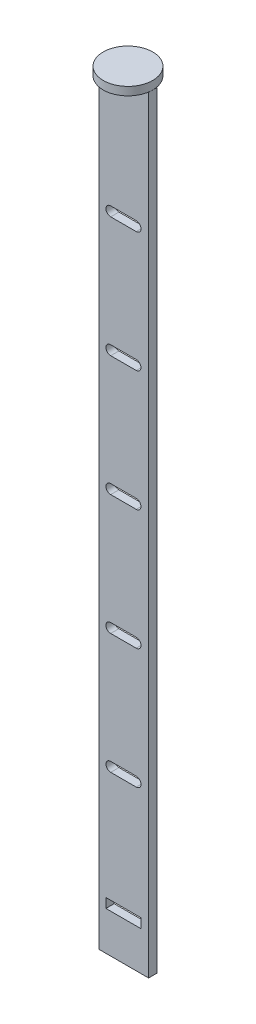
SolidWorks part; units mm, degrees
ref_plane "Front Plane" through (0, 0, 0) normal (0, 0, 1) x (1, 0, 0)
ref_plane "Top Plane" through (0, 0, 0) normal (0, 1, 0) x (1, 0, 0)
ref_plane "Right Plane" through (0, 0, 0) normal (1, 0, 0) x (0, 0, -1)
other "Configuration Table"
sketch "Sketch1" plane through (0, 0, 0) normal (1, 0, 0) x (0, 0, -1)
  line L1 (-495, 46.8667) -> (-501, 46.8667)
  line L2 (-495, 46.8667) -> (-495, 51.4667)
  line L3 (-495, 51.4667) -> (-501, 51.4667)
  line L4 (-501, 46.8667) -> (-501, 51.4667)
  line L5 (-495, 46.8667) -> (-501, 51.4667) construction
  line L6 (-495, 51.4667) -> (-501, 46.8667) construction
  point P0 (-498, 49.1667)
extrude "slot_0" add sketch "Sketch1" along normal blind 16.9953 from offset 20.3047 separate body
sketch "Sketch2" plane through (0, 0, 0) normal (1, 0, 0) x (0, 0, -1)
  line L1 (-496, 28) -> (-500, 28)
  line L2 (-496, 28) -> (-496, 400)
  line L3 (-496, 400) -> (-500, 400)
  line L4 (-500, 28) -> (-500, 400)
  line L5 (-496, 28) -> (-500, 400) construction
  line L6 (-496, 400) -> (-500, 28) construction
  point P0 (-498, 214)
extrude "bar" add sketch "Sketch2" along normal blind 24 from offset 17 separate body
combine bodies "Combine1" operation type subtract main body 103 bodies to subtract 102
sketch "Sketch3" plane through (0, 0, 0) normal (0, 0, 1) x (1, 0, 0)
  circle A0 centre (22.6047, 107.5) radius 2.3
extrude "slot_end_1" add sketch "Sketch3" along normal blind 6 from offset 495 separate body
combine bodies "Combine2" operation type subtract main body 104 bodies to subtract 105
sketch "Sketch4" plane through (0, 0, 0) normal (0, 0, 1) x (1, 0, 0)
  circle A0 centre (35, 107.5) radius 2.3
extrude "slot_end_b_1" add sketch "Sketch4" along normal blind 6 from offset 495 separate body
combine bodies "Combine3" operation type subtract main body 106 bodies to subtract 107
sketch "Sketch5" plane through (0, 0, 0) normal (0, 0, 1) x (1, 0, 0)
  line L1 (22.6047, 105.2) -> (35, 105.2)
  line L2 (22.6047, 105.2) -> (22.6047, 109.8)
  line L3 (22.6047, 109.8) -> (35, 109.8)
  line L4 (35, 105.2) -> (35, 109.8)
  line L5 (22.6047, 105.2) -> (35, 109.8) construction
  line L6 (22.6047, 109.8) -> (35, 105.2) construction
  circle A0 centre (35, 107.5) radius 2.3 construction
  point P0 (28.8024, 107.5)
extrude "Cut-Extrude1" cut sketch "Sketch5" against normal through all and the other way through all
sketch "Sketch6" plane through (0, 0, 0) normal (0, 0, 1) x (1, 0, 0)
  circle A0 centre (22.6047, 165.8333) radius 2.3
extrude "slot_end_2" add sketch "Sketch6" along normal blind 6 from offset 495 separate body
combine bodies "Combine4" operation type subtract main body 109 bodies to subtract 110
sketch "Sketch7" plane through (0, 0, 0) normal (0, 0, 1) x (1, 0, 0)
  circle A0 centre (35, 165.8333) radius 2.3
extrude "slot_end_b_2" add sketch "Sketch7" along normal blind 6 from offset 495 separate body
combine bodies "Combine5" operation type subtract main body 111 bodies to subtract 112
sketch "Sketch8" plane through (0, 0, 0) normal (0, 0, 1) x (1, 0, 0)
  line L1 (22.6047, 163.5333) -> (35, 163.5333)
  line L2 (22.6047, 163.5333) -> (22.6047, 168.1333)
  line L3 (22.6047, 168.1333) -> (35, 168.1333)
  line L4 (35, 163.5333) -> (35, 168.1333)
  line L5 (22.6047, 163.5333) -> (35, 168.1333) construction
  line L6 (22.6047, 168.1333) -> (35, 163.5333) construction
  circle A0 centre (35, 165.8333) radius 2.3 construction
  point P0 (28.8024, 165.8333)
extrude "Cut-Extrude2" cut sketch "Sketch8" against normal through all and the other way through all
sketch "Sketch9" plane through (0, 0, 0) normal (0, 0, 1) x (1, 0, 0)
  circle A0 centre (22.6047, 224.1667) radius 2.3
extrude "slot_end_3" add sketch "Sketch9" along normal blind 6 from offset 495 separate body
combine bodies "Combine6" operation type subtract main body 114 bodies to subtract 115
sketch "Sketch10" plane through (0, 0, 0) normal (0, 0, 1) x (1, 0, 0)
  circle A0 centre (35, 224.1667) radius 2.3
extrude "slot_end_b_3" add sketch "Sketch10" along normal blind 6 from offset 495 separate body
combine bodies "Combine7" operation type subtract main body 116 bodies to subtract 117
sketch "Sketch11" plane through (0, 0, 0) normal (0, 0, 1) x (1, 0, 0)
  line L1 (22.6047, 221.8667) -> (35, 221.8667)
  line L2 (22.6047, 221.8667) -> (22.6047, 226.4667)
  line L3 (22.6047, 226.4667) -> (35, 226.4667)
  line L4 (35, 221.8667) -> (35, 226.4667)
  line L5 (22.6047, 221.8667) -> (35, 226.4667) construction
  line L6 (22.6047, 226.4667) -> (35, 221.8667) construction
  circle A0 centre (35, 224.1667) radius 2.3 construction
  point P0 (28.8024, 224.1667)
extrude "Cut-Extrude3" cut sketch "Sketch11" against normal through all and the other way through all
sketch "Sketch12" plane through (0, 0, 0) normal (0, 0, 1) x (1, 0, 0)
  circle A0 centre (22.6047, 282.5) radius 2.3
extrude "slot_end_4" add sketch "Sketch12" along normal blind 6 from offset 495 separate body
combine bodies "Combine8" operation type subtract main body 119 bodies to subtract 120
sketch "Sketch13" plane through (0, 0, 0) normal (0, 0, 1) x (1, 0, 0)
  circle A0 centre (35, 282.5) radius 2.3
extrude "slot_end_b_4" add sketch "Sketch13" along normal blind 6 from offset 495 separate body
combine bodies "Combine9" operation type subtract main body 121 bodies to subtract 122
sketch "Sketch14" plane through (0, 0, 0) normal (0, 0, 1) x (1, 0, 0)
  line L1 (22.6047, 280.2) -> (35, 280.2)
  line L2 (22.6047, 280.2) -> (22.6047, 284.8)
  line L3 (22.6047, 284.8) -> (35, 284.8)
  line L4 (35, 280.2) -> (35, 284.8)
  line L5 (22.6047, 280.2) -> (35, 284.8) construction
  line L6 (22.6047, 284.8) -> (35, 280.2) construction
  circle A0 centre (35, 282.5) radius 2.3 construction
  point P0 (28.8024, 282.5)
extrude "Cut-Extrude4" cut sketch "Sketch14" against normal through all and the other way through all
sketch "Sketch15" plane through (0, 0, 0) normal (0, 0, 1) x (1, 0, 0)
  circle A0 centre (22.6047, 340.8333) radius 2.3
extrude "slot_end_5" add sketch "Sketch15" along normal blind 6 from offset 495 separate body
combine bodies "Combine10" operation type subtract main body 124 bodies to subtract 125
sketch "Sketch16" plane through (0, 0, 0) normal (0, 0, 1) x (1, 0, 0)
  circle A0 centre (35, 340.8333) radius 2.3
extrude "slot_end_b_5" add sketch "Sketch16" along normal blind 6 from offset 495 separate body
combine bodies "Combine11" operation type subtract main body 126 bodies to subtract 127
sketch "Sketch17" plane through (0, 0, 0) normal (0, 0, 1) x (1, 0, 0)
  line L1 (22.6047, 338.5333) -> (35, 338.5333)
  line L2 (22.6047, 338.5333) -> (22.6047, 343.1333)
  line L3 (22.6047, 343.1333) -> (35, 343.1333)
  line L4 (35, 338.5333) -> (35, 343.1333)
  line L5 (22.6047, 338.5333) -> (35, 343.1333) construction
  line L6 (22.6047, 343.1333) -> (35, 338.5333) construction
  circle A0 centre (35, 340.8333) radius 2.3 construction
  point P0 (28.8024, 340.8333)
extrude "Cut-Extrude5" cut sketch "Sketch17" against normal through all and the other way through all
sketch "Sketch18" plane through (0, 0, 0) normal (0, 1, 0) x (1, 0, 0)
  circle A0 centre (29, -498) radius 12
extrude "crosshead" add sketch "Sketch18" along normal blind 4 from offset 400 separate body
